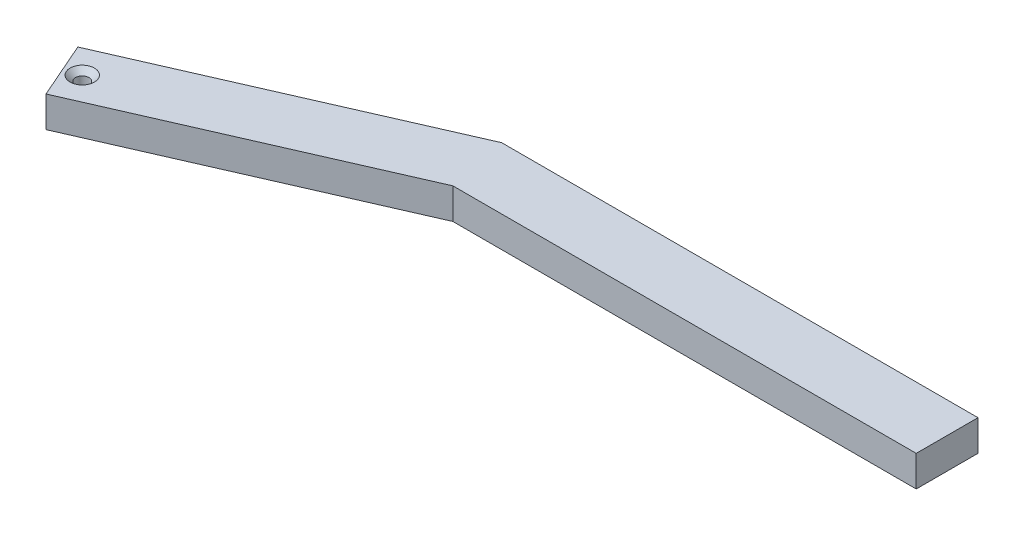
SolidWorks part; units mm, degrees
ref_plane "Front Plane" through (0, 0, 0) normal (0, 0, 1) x (1, 0, 0)
ref_plane "Top Plane" through (0, 0, 0) normal (0, 1, 0) x (1, 0, 0)
ref_plane "Right Plane" through (0, 0, 0) normal (1, 0, 0) x (0, 0, -1)
sketch "Sketch1" plane through (0, 0, 0) normal (0, 1, 0) x (1, 0, 0)
  line L0 (0, 0) -> (242.4215, 106.1223)
  line L1 (242.4215, 106.1223) -> (634.0535, 106.1223)
  line L2 (634.0535, 106.1223) -> (634.0535, 55.3223)
  line L3 (634.0535, 55.3223) -> (253.0535, 55.3223)
  line L4 (253.0535, 55.3223) -> (20.3717, -46.5364)
  line L5 (20.3717, -46.5364) -> (0, 0)
  dimension "D1" = 381
  dimension "D2" = 254
  dimension "D3" = 50.8
  dimension "D4" = 50.8
extrude "Boss-Extrude1" add sketch "Sketch1" along normal blind 25.4
hole_wizard "CSK for M10 Flat Head Machine Screw1" positions "Sketch4" profile "Sketch5" countersink size "M10" standard "ANSI Metric" end condition up to next
sketch "Sketch4" plane through (0, 25.4, 0) normal (0, 1, 0) x (1, 0, 0)
  line L0 (10.1859, -23.2682) -> (53.5308, -4.2935) construction
  line L1 (0, 0) -> (20.3717, -46.5364) construction
  point P0 (21.82, -18.1752)
  dimension "D1" = 12.7
sketch "Sketch5" plane through (21.82, 25.4, 18.1752) normal (1, 0, 0) x (0, 0, 1)
  line L0 (0, 0) -> (0, 25.4)
  line L1 (0, 25.4) -> (5.5, 25.4)
  line L2 (5.5, 25.4) -> (5.5, 4.5)
  line L3 (5.5, 4.5) -> (10, 0)
  line L5 (10, 0) -> (0, 0)
  line L6 (-5.5, 4.5) -> (-10, 0) construction
  line L11 (0, -6.35) -> (0, 107.95) construction
  dimension "Thru Hole Dia." = 11
  dimension "Thru Hole Depth" = 25.4
  dimension "Near C'Sink Dia." = 20
  dimension "Near C'Sink Angle" = 90
